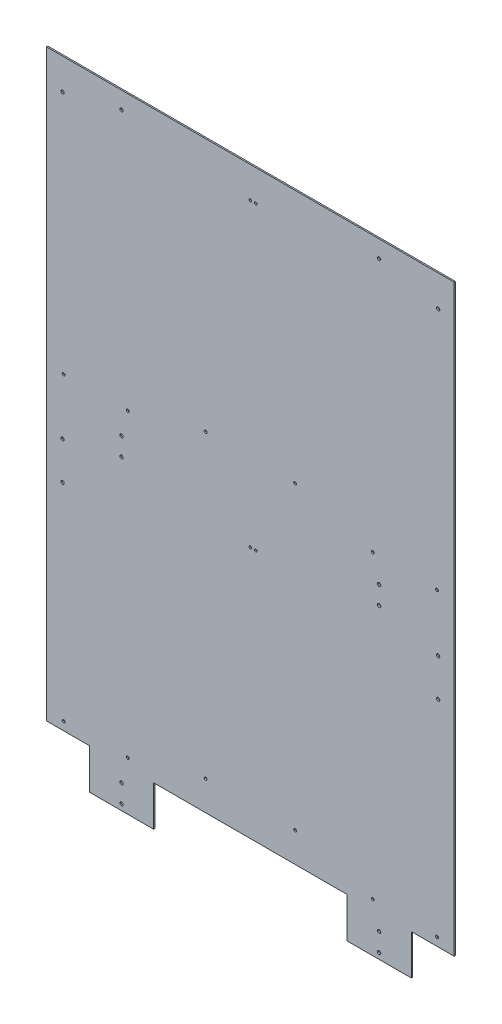
SolidWorks part; units mm, degrees
material "PC High Viscosity"
ref_plane "Front Plane" through (0, 0, 0) normal (0, 0, 1) x (1, 0, 0)
ref_plane "Top Plane" through (0, 0, 0) normal (0, 1, 0) x (1, 0, 0)
ref_plane "Right Plane" through (0, 0, 0) normal (1, 0, 0) x (0, 0, -1)
sketch "Sketch2" plane through (0, 0, 0) normal (0, 0, 1) x (1, 0, 0)
  line L0 (-482.6, 0) -> (-381, 0)
  line L2 (-482.6, 0) -> (-482.6, 1409.7)
  line L3 (-482.6, 1409.7) -> (482.6, 1409.7)
  line L4 (482.6, 0) -> (482.6, 1409.7)
  line L5 (-381, 0) -> (-381, -95.25)
  line L6 (-381, -95.25) -> (-228.6, -95.25)
  line L7 (-228.6, -95.25) -> (-228.6, 0)
  line L8 (-228.6, 0) -> (228.6, 0)
  line L9 (228.6, 0) -> (228.6, -95.25)
  line L10 (228.6, -95.25) -> (381, -95.25)
  line L11 (381, -95.25) -> (381, 0)
  line L12 (381, 0) -> (482.6, 0)
  line L13 (0, 0) -> (0, 1409.7) construction
  dimension "D2" = 965.2
  dimension "D1" = 1409.7
  dimension "D3" = 95.25
  dimension "D5" = 152.4
  dimension "D4" = 457.2
extrude "Boss-Extrude1" add sketch "Sketch2" along normal blind 3.175
hole_wizard "1/4 Clearance Hole1" positions "Sketch3" profile "Sketch4" hole size "1/4" standard "ANSI Inch" end condition through all
sketch "Sketch3" plane through (0, 0, 3.175) normal (0, 0, 1) x (1, 0, 0)
  line L0 (0, 0) -> (0, 1409.7) construction
  line L4 (-9.861, 81.3082) -> (0, 118.11) construction
  line L5 (-9.861, 81.3082) -> (472.739, -48.0041) construction
  line L6 (0, 118.11) -> (482.6, -11.2023) construction
  line L7 (472.739, -48.0041) -> (482.6, -11.2023) construction
  line L8 (482.6, 0) -> (482.6, 1409.7) construction
  line L9 (12.7, 114.707) -> (2.839, 77.9053) construction
  line L11 (-4.9305, 99.7091) -> (477.6695, -29.6032) construction
  line L13 (289.9164, 20.7051) -> (289.9164, 731.9051) construction
  line L14 (0, 118.11) -> (1.6435, 124.2436) construction
  line L15 (0, 118.11) -> (480.9565, -10.7619) construction
  line L16 (1.6435, 124.2436) -> (482.6, -4.6283) construction
  line L17 (480.9565, -10.7619) -> (482.6, -4.6283) construction
  line L18 (482.6, 1409.7) -> (-482.6, 1409.7) construction
  line L20 (-228.6, 0) -> (228.6, 0) construction
  line L21 (-381, -95.25) -> (-228.6, -95.25) construction
  circle A0 centre (441.96, 19.4092) radius 6.35 construction
  point P178 (105.9076, 70.0101)
  point P180 (289.9164, 20.7051)
  point P183 (-289.9164, 20.7051)
  point P184 (-105.9076, 70.0101)
  point P195 (105.9076, 781.2101)
  point P196 (289.9164, 731.9051)
  point P197 (-289.9164, 731.9051)
  point P198 (-105.9076, 781.2101)
  point P566 (441.96, 19.4092)
  point P569 (-441.96, 19.4092)
  point P573 (-441.96, 730.6092)
  point P576 (441.96, 730.6092)
  dimension "D10" = 12.7
  dimension "D11" = 6.35
  dimension "D2" = 12.7
  dimension "D3" = 38.1
  dimension "D4" = 213.36
  dimension "D5" = 101.6
  dimension "D6" = 292.1
  dimension "D8" = 711.2
  dimension "D9" = 6.35
  dimension "D12" = 439.2982
  dimension "D13" = 15
  dimension "D14" = 441.96
  dimension "D7" = 2
sketch "Sketch4" plane through (441.96, 730.6092, 3.175) normal (1, 0, 0) x (0, -1, 0)
  line L0 (0, 0) -> (0, 3.175)
  line L1 (0, 3.175) -> (3.3782, 3.175)
  line L2 (3.3782, 3.175) -> (3.3782, 0)
  line L5 (3.3782, 0) -> (0, 0)
  line L11 (0, -6.35) -> (0, 107.95) construction
  dimension "Thru Hole Dia." = 6.7564
  dimension "Thru Hole Depth" = 3.175
hole_wizard "5/16 (0.3125) Diameter Hole1" positions "Sketch5" profile "Sketch6" hole size "5/16" standard "ANSI Inch" end condition through all
sketch "Sketch5" plane through (0, 0, 3.175) normal (0, 0, 1) x (1, 0, 0)
  line L0 (0, 1409.7) -> (0, -95.25) construction
  line L1 (482.6, 1409.7) -> (-482.6, 1409.7) construction
  line L3 (-482.6, 1381.76) -> (482.6, 1381.76) construction
  line L4 (-482.6, 1381.76) -> (-482.6, 1343.66) construction
  line L5 (-482.6, 1343.66) -> (482.6, 1343.66) construction
  line L6 (482.6, 1381.76) -> (482.6, 1343.66) construction
  line L7 (-482.6, 1409.7) -> (-482.6, 0) construction
  line L8 (482.6, 0) -> (482.6, 1409.7) construction
  line L9 (-304.8, -95.25) -> (-304.8, 1409.7) construction
  line L10 (-381, -95.25) -> (-228.6, -95.25) construction
  point P13 (-304.8, 1341.12)
  point P17 (304.8, 1341.12)
  point P181 (-304.8, 673.1)
  point P182 (-304.8, 629.92)
  point P183 (304.8, 673.1)
  point P184 (304.8, 629.92)
  point P185 (-304.8, -38.1)
  point P186 (-304.8, -81.28)
  point P187 (304.8, -38.1)
  point P188 (304.8, -81.28)
  point P189 (-444.5, 1308.1)
  point P191 (444.5, 1308.1)
  point P200 (-444.5, 596.9)
  point P201 (444.5, 596.9)
  point P211 (-444.5, 508)
  point P213 (444.5, 508)
  dimension "D1" = 38.1
  dimension "D2" = 27.94
  dimension "D3" = 43.18
  dimension "D4" = 2.54
  dimension "D6" = 711.2
  dimension "D7" = 444.5
  dimension "D8" = 101.6
  dimension "D10" = 711.2
  dimension "D11" = 43.18
  dimension "D12" = 88.9
  dimension "D5" = 3
  dimension "D9" = 2
sketch "Sketch6" plane through (444.5, 508, 3.175) normal (1, 0, 0) x (0, -1, 0)
  line L0 (0, 0) -> (0, 3.175)
  line L1 (0, 3.175) -> (3.9687, 3.175)
  line L2 (3.9687, 3.175) -> (3.9687, 0)
  line L5 (3.9687, 0) -> (0, 0)
  line L11 (0, -6.35) -> (0, 107.95) construction
  dimension "Thru Hole Dia." = 7.9375
  dimension "Thru Hole Depth" = 3.175
sketch "Sketch7" plane through (0, 0, 3.175) normal (0, 0, 1) x (1, 0, 0)
  line L0 (482.6, 0) -> (482.6, 1409.7) construction
  line L1 (-482.6, 1409.7) -> (482.6, 1409.7)
  line L2 (-482.6, 1409.7) -> (-482.6, 1381.76)
  line L3 (-482.6, 1381.76) -> (482.6, 1381.76)
  line L4 (482.6, 1409.7) -> (482.6, 1381.76)
  dimension "D1" = 27.94
extrude "Cut-Extrude1" cut sketch "Sketch7" against normal through all
hole_wizard "1/4 (0.25) Diameter Hole1" positions "Sketch8" profile "Sketch9" hole size "1/4" standard "ANSI Inch" end condition through all
sketch "Sketch8" plane through (0, 0, 3.175) normal (0, 0, 1) x (1, 0, 0)
  line L1 (0, 1308.1) -> (-444.5, 1308.1)
  point P0 (0, 1308.1)
  point P2 (0, 596.9)
  point P14 (12.7, 1308.1)
  point P16 (12.7, 596.9)
  point P19 (0, 0)
  point P20 (0, 0)
  point P21 (12.33, 1311.1434)
  point P22 (0, 0)
  dimension "D1" = 12.7
  dimension "D2" = 711.2
sketch "Sketch9" plane through (0, 1308.1, 3.175) normal (1, 0, 0) x (0, -1, 0)
  line L0 (0, 0) -> (0, 3.175)
  line L1 (0, 3.175) -> (3.175, 3.175)
  line L2 (3.175, 3.175) -> (3.175, 0)
  line L5 (3.175, 0) -> (0, 0)
  line L11 (0, -6.35) -> (0, 107.95) construction
  dimension "Thru Hole Dia." = 6.35
  dimension "Thru Hole Depth" = 3.175
equation "\"D3@Sketch2\"=59.25-\"D1@Sketch2\""
